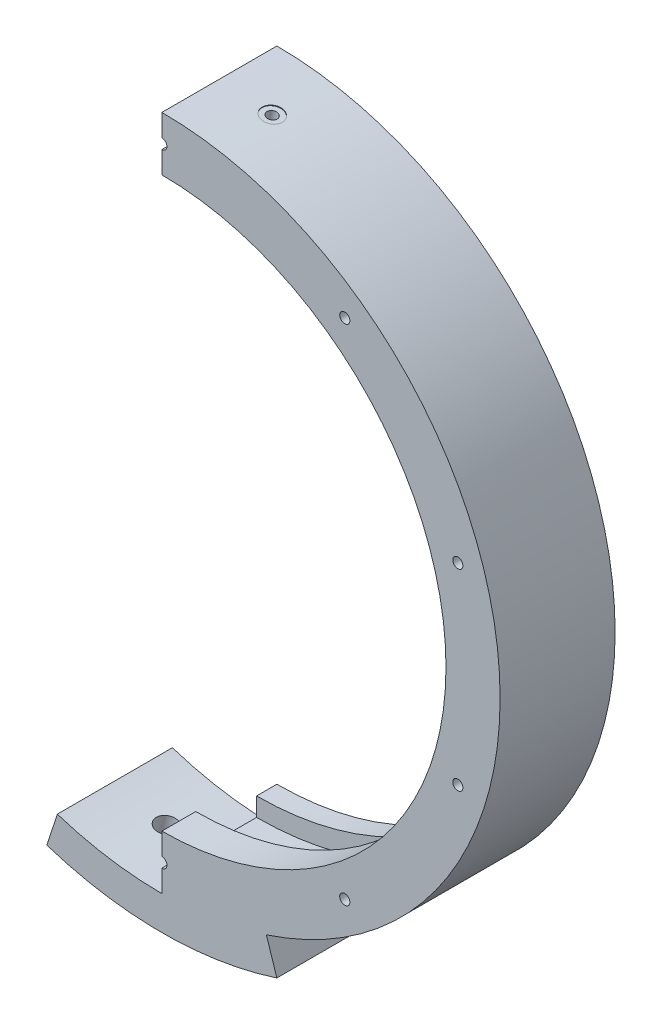
SolidWorks part; units mm, degrees
ref_plane "前视基准面" through (0, 0, 0) normal (0, 0, 1) x (1, 0, 0)
ref_plane "上视基准面" through (0, 0, 0) normal (0, 1, 0) x (1, 0, 0)
ref_plane "右视基准面" through (0, 0, 0) normal (1, 0, 0) x (0, 0, -1)
other "Configuration Table"
sketch "草图1" plane through (0, 0, 0) normal (0, 0, 1) x (1, 0, 0)
  circle A5 centre (0, 0) radius 47.25
  circle A6 centre (0, 0) radius 49.25
  circle A7 centre (0, 0) radius 44.5
  circle A8 centre (0, 0) radius 42
  dimension "D1" = 94.5
  dimension "D2" = 2
  dimension "D3" = 89
  dimension "D4" = 84
extrude "凸台-拉伸1" add sketch "草图1" along normal blind 17 contours A6 | A7
extrude "切除-拉伸2" cut sketch "草图1<5>" against normal offset from surface (14 mm away) 3 from surface contours A5 up to face at (49.25, 0, 0) starting at face at (49.25, 0, 17)
sketch "草图1<5>" plane through (0, 0, 0) normal (0, 0, 1) x (1, 0, 0) same geometry as "草图1"
extrude "凸台-拉伸2" add sketch "草图1<6>" against normal blind 5 from surface contours A6 | A8 starting at face at (47.25, 0, 17)
sketch "草图1<6>" plane through (0, 0, 0) normal (0, 0, 1) x (1, 0, 0) same geometry as "草图1"
sketch "草图2" plane through (0, 0, 17) normal (0, 0, 1) x (1, 0, 0)
  line L0 (0, 50) -> (0, 42) construction
  circle A0 centre (0, 0) radius 50
  circle A2 centre (0, 0) radius 49.25
  circle A3 centre (0, 0) radius 49.25 construction
  circle A4 centre (0, 46) radius 0.75
  circle A6 centre (0, 0) radius 42 construction
  dimension "D1" = 100
  dimension "D2" = 1.5
extrude "凸台-拉伸3" add sketch "草图2" against normal through all contours A0 | A2
extrude "切除-拉伸3" cut sketch "草图2<4>" against normal blind 4 contours A4
sketch "草图2<4>" plane through (0, 0, 17) normal (0, 0, 1) x (1, 0, 0) same geometry as "草图2"
pattern_circular "阵列(圆周)1" count 10 over 360 about axis through (0, 0, 12) along (0, 0, 1) of "切除-拉伸3" reverse direction yes
ref_plane "基准面1" through (0, 0, 8.5) normal (0, 0, 1) x (1, 0, 0)
sketch "草图3" plane through (0, 0, 8.5) normal (0, 0, 1) x (1, 0, 0)
  line L0 (16.9959, 52.3081) -> (-16.9959, -52.3081)
  line L1 (7.0653, 49.403) -> (7.8061, 49.2856)
  line L2 (7.8217, 49.3844) -> (-7.8217, -49.3844)
  line L4 (-16.9959, 52.3081) -> (16.9959, -52.3081)
  line L8 (6.8095, 52.5821) -> (8.291, 52.3475)
  line L9 (6.8095, 52.5821) -> (6.3245, 49.5203)
  line L10 (6.3245, 49.5203) -> (7.8061, 49.2856)
  line L11 (8.291, 52.3475) -> (7.8061, 49.2856)
  line L12 (7.0653, 49.403) -> (6.4396, 45.4522)
  line L13 (7.8061, 49.2856) -> (7.1803, 45.3349)
  line L14 (6.4396, 45.4522) -> (7.1803, 45.3349)
  line L15 (6.3816, 54.6748) -> (8.6039, 54.3229)
  line L16 (6.3816, 54.6748) -> (6.0687, 52.6995)
  line L17 (8.6039, 54.3229) -> (8.291, 52.3475)
  line L18 (6.0687, 52.6995) -> (8.291, 52.3475)
  line L19 (0, 96.1886) -> (0, -87.33) construction
  circle A0 centre (0, 0) radius 50 construction
  arc A1 (-16.9959, 52.3081) -> (16.9959, 52.3081) centre (0, 0) cw
  arc A2 (16.9959, -52.3081) -> (-16.9959, -52.3081) centre (0, 0) cw
  circle A4 centre (0, 0) radius 50
  dimension "D5" = 5
  dimension "D1" = 2
  dimension "D2" = 9
  dimension "D3" = 2.25
  dimension "D4" = 36
  dimension "D6" = 1.5
  dimension "D7" = 3.1
  dimension "D8" = 4
  dimension "D9" = 0.75
  dimension "D10" = 18
extrude "凸台-拉伸4" add sketch "草图3" against normal up to surface (8.5 mm away) from surface contours L19 A1 L4 A4 | A1 L19 A4 L9 L18 L16 | A4 L0 A1 L17 L11 | A4 L11 L8 L9 | A1 L16 L18 L8 L17 region at (12.2525, 51.0355, 8.5) region at (7.3394, 53.5029, 8.5) region at (7.3141, 50.9797, 8.5) region at (3.225, 52.3487, 8.5) region at (-8.1853, 51.6797, 8.5) up to face at (44.5, 0, 0) starting at face at (-26.4314, 37.6556, 17)
revolve "切除-旋转1" cut sketch "草图3<5>" angle 360 about L2
sketch "草图3<5>" plane through (0, 0, 8.5) normal (0, 0, 1) x (1, 0, 0) same geometry as "草图3"
pattern_circular "阵列(圆周)2" count 2 over 360 about axis through (0, 0, 0) along (0, 0, 1) of "凸台-拉伸4", "切除-旋转1" reverse direction yes
sketch "草图4" plane through (0, 0, 8.5) normal (0, 0, 1) x (1, 0, 0)
  line L0 (16.9959, 52.3081) -> (-16.9959, -52.3081)
  line L1 (0, 55) -> (0, -55)
  line L2 (-16.9959, 52.3081) -> (16.9959, -52.3081)
  circle A0 centre (0, 0) radius 55
  circle A1 centre (0, 0) radius 50
  arc A2 (15.4508, -47.5528) -> (15.4508, 47.5528) centre (0, 0) ccw construction
extrude "切除-拉伸5" cut sketch "草图4" against normal through all both and the other way through all contours L2 A0 L0 | L1 A0 L2 | L2 A1 L0 | L1 A1 L2 | L0 A1 L1 | A1 L0 A0 L1 region at (8.1853, 51.6797, 8.5) region at (-8.1853, 51.6797, 8.5) region at (-5.1931, -32.7877, 8.5) region at (-5.1931, 32.7877, 8.5) region at (-25.2276, 0, 8.5) region at (-17.2871, 49.5849, 8.5)
